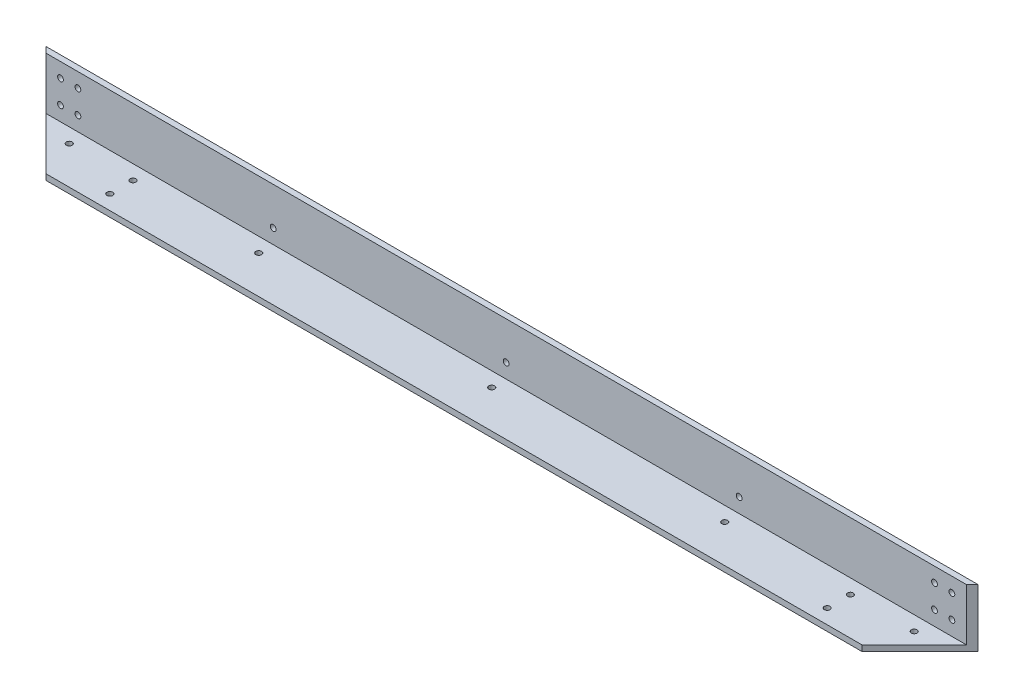
SolidWorks part; units mm, degrees
ref_plane "Front Plane" through (0, 0, 0) normal (0, 0, 1) x (1, 0, 0)
ref_plane "Top Plane" through (0, 0, 0) normal (0, 1, 0) x (1, 0, 0)
ref_plane "Right Plane" through (0, 0, 0) normal (1, 0, 0) x (0, 0, -1)
sketch "Sketch1" plane through (0, 0, 0) normal (1, 0, 0) x (0, 0, -1)
  line L0 (0, 0) -> (-31.75, 0)
  line L1 (-31.75, 0) -> (-31.75, 3.175)
  line L2 (-31.75, 3.175) -> (-3.175, 3.175)
  line L3 (-3.175, 3.175) -> (-3.175, 31.75)
  line L4 (-3.175, 31.75) -> (0, 31.75)
  line L5 (0, 31.75) -> (0, 0)
  dimension "LHeight" = 31.75
  dimension "LWidth" = 31.75
  dimension "LMaterialThickness" = 3.175
  dimension "D1" = 28.575
  dimension "D2" = 28.575
  dimension "D3" = 3.175
extrude "Boss-Extrude1" add sketch "Sketch1" along normal blind 510
chamfer "Chamfer6" distance 31.75 angle 45 1 edges at (510, 1.5875, 31.75)
chamfer "Chamfer7" distance 31.75 angle 45 1 edges at (0, 1.5875, 31.75)
sketch "TopHoles-Sketch3" plane through (0, 3.175, 0) normal (0, 1, 0) x (1, 0, 0)
  line L1 (478.25, -31.75) -> (31.75, -31.75) construction
  line L2 (510, 0) -> (0, 0) construction
  circle A5 centre (58.7375, -23.8125) radius 1.5875
  circle A6 centre (451.2625, -23.8125) radius 1.5875
  circle A9 centre (451.2625, -11.1125) radius 1.5875
  circle A10 centre (58.7375, -11.1125) radius 1.5875
  circle A11 centre (486.1875, -11.1125) radius 1.5875
  circle A12 centre (23.8125, -11.1125) radius 1.5875
  circle A13 centre (127.5, -11.1125) radius 1.5875
  circle A14 centre (255, -11.1125) radius 1.5875
  circle A15 centre (382.5, -11.1125) radius 1.5875
  dimension "D10" = 127.5
  dimension "D9" = 3.175
  dimension "D12" = 7.9375
  dimension "D2" = 11.1125
  dimension "D3" = 23.8125
  dimension "D6" = 23.8125
  dimension "D4" = 34.925
  dimension "D5" = 12.7
  dimension "D7" = 34.925
  dimension "D11" = 127.5
  dimension "D13" = 127.5
extrude "TopHoles-Cut-Extrude2" cut sketch "TopHoles-Sketch3" against normal through all
sketch "FrontHoles-Sketch4" plane through (0, 0, 3.175) normal (0, 0, 1) x (1, 0, 0)
  line L0 (0, 0) -> (0, 31.75) construction
  line L1 (510, 0) -> (510, 31.75) construction
  line L2 (510, 0) -> (0, 0) construction
  line L7 (510, 0) -> (0, 0) construction
  line L8 (510, 31.75) -> (0, 31.75) construction
  circle A1 centre (11.1125, 23.8125) radius 1.5875
  circle A3 centre (489.3625, 23.8125) radius 1.5875
  circle A4 centre (20.6375, 23.8125) radius 1.5875
  circle A5 centre (498.8875, 23.8125) radius 1.5875
  circle A6 centre (11.1125, 11.1125) radius 1.5875
  circle A7 centre (20.6375, 11.1125) radius 1.5875
  circle A8 centre (489.3625, 11.1125) radius 1.5875
  circle A9 centre (498.8875, 11.1125) radius 1.5875
  circle A10 centre (127.5, 11.1125) radius 1.5875
  circle A11 centre (255, 11.1125) radius 1.5875
  circle A12 centre (382.5, 11.1125) radius 1.5875
  dimension "D2" = 3.175
  dimension "D7" = 11.1125
  dimension "D4" = 7.9375
  dimension "D1" = 11.1125
  dimension "D6" = 20.6375
  dimension "D3" = 11.1125
  dimension "D5" = 20.6375
  dimension "D8" = 127.5
  dimension "D9" = 127.5
  dimension "D10" = 127.5
extrude "FrontHoles-Cut-Extrude3" cut sketch "FrontHoles-Sketch4" against normal through all
equation "\"TopRailWidth\"= 1.25in"
equation "\"TopRailHeight\"= 1.25in"
equation "\"RailThickness\"= .125in'Spec"
equation "\"SideRailHoleY1FromEdge\"= \"HoleOffsetFromEdge\""
equation "\"SideRailHoleX1FromSide\"= \"HoleOffsetFromSide\""
equation "\"FrontBackRailLength\"= 510mm"
equation "\"VSWidth\"= 1.25in'Spec"
equation "\"HoleOffsetFromEdge\"= \"RailThickness\" * 2.5"
equation "\"HoleOffsetFromSide\"= \"RailThickness\" * 3.5"
equation "\"TopCBWidth\"= \"TopRailWidth\" - \"RailThickness\"'Equals 28.575"
equation "\"SideRailHoleX2FromSide\"= \"VSWidth\" - \"HoleOffsetFromEdge\" - \"RailThickness\"'Equals 20.6375"
equation "\"FasteningHoleDiameter\"= .125in"
equation "\"SideRailHoleY2FromSide\"= \"HoleOffsetFromSide\""
equation "\"D2@FrontHoles-Sketch4\"=\"FasteningHoleDiameter\""
equation "\"LWidth@Sketch1\"=\"TopRailWidth\""
equation "\"LHeight@Sketch1\"=\"TopRailHeight\""
equation "\"LMaterialThickness@Sketch1\"=\"RailThickness\""
equation "\"D1@Boss-Extrude1\"= \"FrontBackRailLength\""
equation "\"D7@FrontHoles-Sketch4\"=\"SideRailHoleY2FromSide\""
equation "\"D4@FrontHoles-Sketch4\"=\"SideRailHoleY1FromEdge\""
equation "\"D1@Chamfer6\"=\"TopRailWidth\""
equation "\"D1@Chamfer7\"=\"TopRailWidth\""
equation "\"D3@TopHoles-Sketch3\"=\"TopHoleX1FromEdge\" + \"RailThickness\" "
equation "\"D6@TopHoles-Sketch3\"=\"TopHoleX1FromEdge\" + \"RailThickness\""
equation "\"D1@FrontHoles-Sketch4\"=\"SideRailHoleX1FromSide\""
equation "\"D6@FrontHoles-Sketch4\"=\"SideRailHoleX2FromSide\""
equation "\"D5@FrontHoles-Sketch4\"=\"SideRailHoleX2FromSide\""
equation "\"D3@FrontHoles-Sketch4\"=\"SideRailHoleX1FromSide\""
equation "\"TopHoleX1FromEdge\"= \"TopCBWidth\" - \"HoleOffsetFromEdge\"'Equals 20.6375"
equation "\"TopHoleX2FromX1\"= \"TopCBLength\" - \"TopHoleX1FromEdge\" - \"HoleOffsetFromEdge\"'Equals 34.925"
equation "\"TopHoleY1FromSide\"= \"HoleOffsetFromSide\""
equation "\"TopHoleY2FromY1\"= \"TopCBWidth\" - \"TopHoleY1FromEdge\" - \"HoleOffsetFromEdge\"'Equals 12.7"
equation "\"D2@TopHoles-Sketch3\"=\"TopHoleY1FromSide\""
equation "\"D4@TopHoles-Sketch3\"=\"TopHoleX2FromX1\""
equation "\"D5@TopHoles-Sketch3\"=\"TopHoleY2FromY1\""
equation "\"D7@TopHoles-Sketch3\"=\"TopHoleX2FromX1\""
equation "\"TopCBLength\"= \"TopRailWidth\" * 2'Equals 63.5"
equation "\"TopHoleY1FromEdge\"= \"HoleOffsetFromEdge\""
equation "\"FrontOrBackEnclosureOffsets\"= \"FrontBackRailLength\" / 4"
equation "\"D10@TopHoles-Sketch3\"=\"FrontOrBackEnclosureOffsets\""
equation "\"D11@TopHoles-Sketch3\"=\"FrontOrBackEnclosureOffsets\""
equation "\"D13@TopHoles-Sketch3\"=\"FrontOrBackEnclosureOffsets\""
equation "\"D8@FrontHoles-Sketch4\"=\"FrontOrBackEnclosureOffsets\""
equation "\"D9@FrontHoles-Sketch4\"=\"FrontOrBackEnclosureOffsets\""
equation "\"D10@FrontHoles-Sketch4\"=\"FrontOrBackEnclosureOffsets\""
